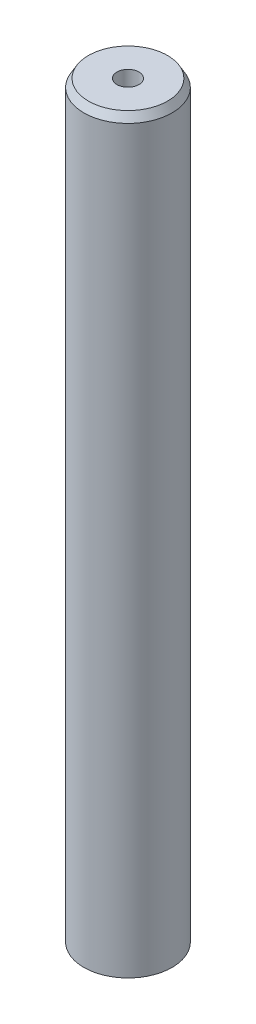
SolidWorks part; units mm, degrees
ref_plane "Front Plane" through (0, 0, 0) normal (0, 0, 1) x (1, 0, 0)
ref_plane "Top Plane" through (0, 0, 0) normal (0, 1, 0) x (1, 0, 0)
ref_plane "Right Plane" through (0, 0, 0) normal (1, 0, 0) x (0, 0, -1)
sketch "Sketch1" plane through (0, 0, 0) normal (0, 1, 0) x (1, 0, 0)
  circle A0 centre (0, 0) radius 5
  dimension "SHAFT_OD" = 10
extrude "Boss-Extrude1" add sketch "Sketch1" along normal blind 85.2775
sketch "Sketch2" plane through (0, 0, 0) normal (0, 1, 0) x (1, 0, 0)
  circle A0 centre (0, 0) radius 1.2434
  dimension "BORE_D" = 2.4869
extrude "Cut-Extrude1" cut sketch "Sketch2" along normal through all
chamfer "Chamfer1" distance 0.896 angle 30 2 edges at (0, 85.2775, 5) (0, 0, 5) first distance on face at (0, 85.2775, 5) first distance on face at (0, 0, 1.2434)
